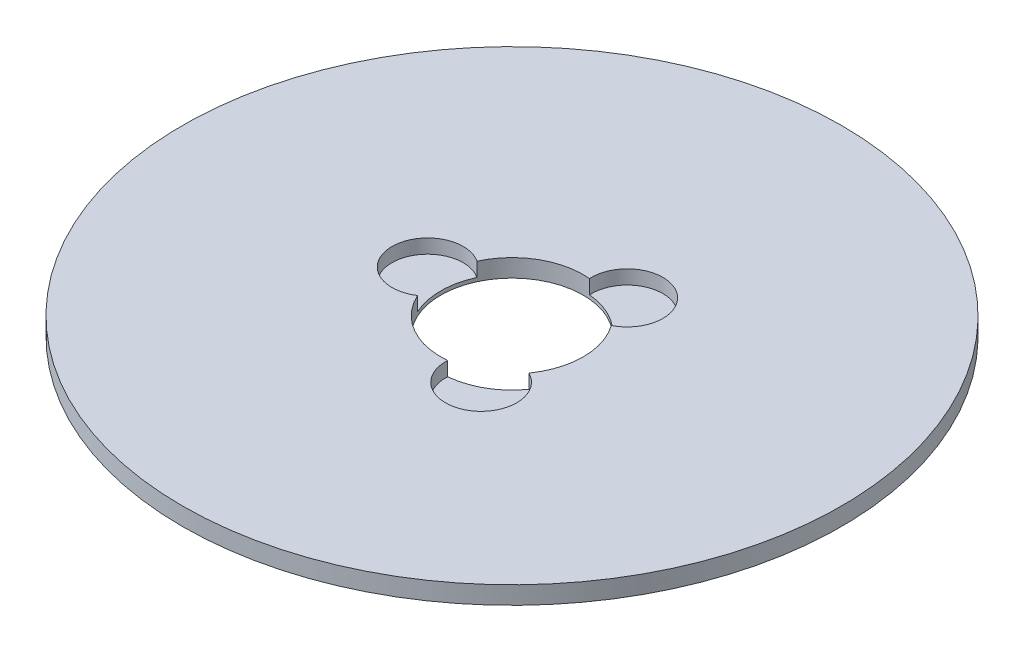
SolidWorks part; units mm, degrees
ref_plane "Front Plane" through (0, 0, 0) normal (0, 0, 1) x (1, 0, 0)
ref_plane "Top Plane" through (0, 0, 0) normal (0, 1, 0) x (1, 0, 0)
ref_plane "Right Plane" through (0, 0, 0) normal (1, 0, 0) x (0, 0, -1)
sketch "Sketch1" plane through (0, 0, 0) normal (0, 1, 0) x (1, 0, 0)
  circle A0 centre (0, 0) radius 92.5
  dimension "FLANGE_OD" = 185
extrude "Boss-Extrude1" add sketch "Sketch1" along normal blind 5
sketch "Sketch2" plane through (0, 0, 0) normal (0, 1, 0) x (1, 0, 0)
  circle A0 centre (0, 0) radius 20
  dimension "BORE_D" = 40
extrude "Cut-Extrude1" cut sketch "Sketch2" along normal through all
sketch "Sketch3" plane through (0, 5, 0) normal (0, 1, 0) x (1, 0, 0)
  circle A0 centre (0, 0) radius 23.682 construction
  circle A1 centre (-23.682, 0) radius 10
  dimension "BOLT_D" = 20
  dimension "BOLT_PCD" = 47.3641
extrude "Cut-Extrude2" cut sketch "Sketch3" against normal blind 3.9508
pattern_circular "CirPattern1" count 3 over 360 about axis through (0, 0, 0) along (0, 1, 0) of "Cut-Extrude2"
